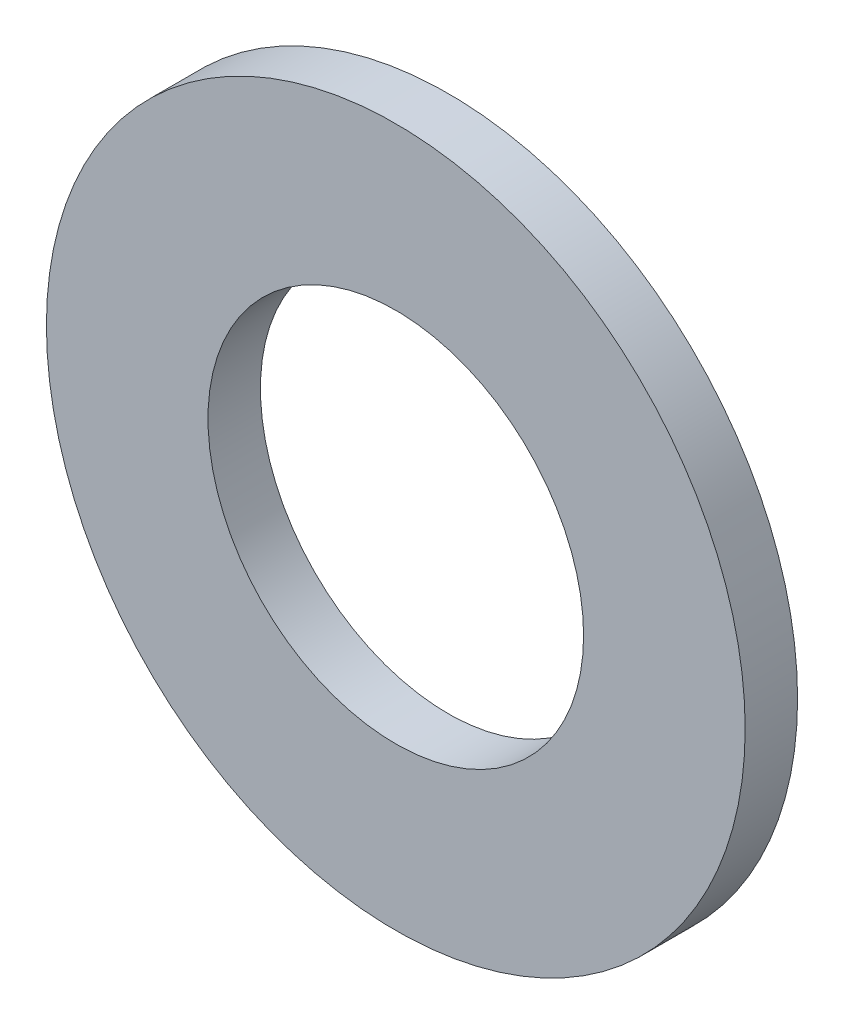
SolidWorks part; units mm, degrees
material "Stainless Steel (ferritic)"
ref_plane "Front Plane" through (0, 0, 0) normal (0, 0, 1) x (1, 0, 0)
ref_plane "Top Plane" through (0, 0, 0) normal (0, 1, 0) x (1, 0, 0)
ref_plane "Right Plane" through (0, 0, 0) normal (1, 0, 0) x (0, 0, -1)
sketch "Sketch1" plane through (0, 0, 0) normal (0, 0, 1) x (1, 0, 0)
  circle A0 centre (0, 0) radius 4
  circle A1 centre (0, 0) radius 2.15
  dimension "OD" = 8
  dimension "ID1" = 4.3
extrude "Boss-Extrude1" add sketch "Sketch1" along normal blind 0.6
ref_axis "Center Axis 1" through (0, 0, 0.6) along (0, 0, -1)
ref_plane "Contact Plane 1" through (0, 0, 0.6) normal (0, 0, 1) x (1, 0, 0)
ref_plane "Contact Plane 2" through (0, 0, 0) normal (0, 0, -1) x (-1, 0, 0)
